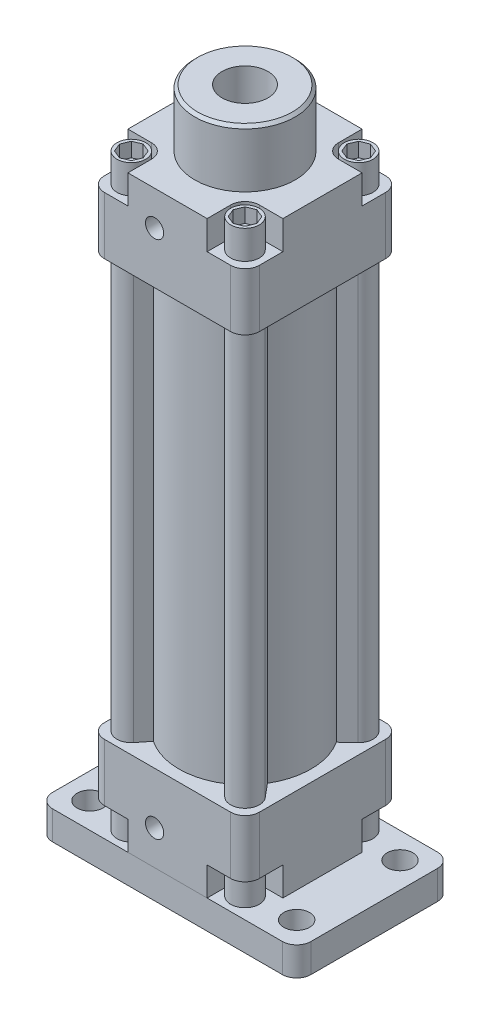
SolidWorks part; units mm, degrees
ref_plane "Front Plane" through (0, 0, 0) normal (0, 0, 1) x (1, 0, 0)
ref_plane "Top Plane" through (0, 0, 0) normal (0, 1, 0) x (1, 0, 0)
ref_plane "Right Plane" through (0, 0, 0) normal (1, 0, 0) x (0, 0, -1)
sketch "Sketch1" plane through (0, 0, 0) normal (0, 1, 0) x (1, 0, 0)
  line L1 (-27, 27) -> (27, 27)
  line L2 (-27, 27) -> (-27, -27)
  line L3 (-27, -27) -> (27, -27)
  line L4 (27, 27) -> (27, -27)
  line L5 (-27, 27) -> (27, -27) construction
  line L6 (-27, -27) -> (27, 27) construction
  point P0 (0, 0)
  dimension "D1" = 54
  dimension "D2" = 54
extrude "Boss-Extrude1" add sketch "Sketch1" along normal blind 20
sketch "Sketch2" plane through (0, 0, 0) normal (0, -1, 0) x (1, 0, 0)
  line L0 (0, 52.3019) -> (0, -54.3704) construction
  line L1 (-79.2133, 0) -> (82.1089, 0) construction
  line L2 (0, 0) -> (32.1456, -32.1456) construction
  line L3 (0, 0) -> (32.1456, 32.1456) construction
  line L4 (-13.799, 23.799) -> (-13.799, 27)
  line L5 (13.799, 23.799) -> (13.799, 27)
  line L6 (-13.799, 27) -> (13.799, 27)
  line L8 (-23.799, 13.799) -> (-27, 13.799)
  line L9 (-23.3345, 23.3345) -> (24.799, -24.799) construction
  line L10 (-24.799, -24.799) -> (24.799, 24.799) construction
  line L11 (-23.799, -13.799) -> (-27, -13.799)
  line L12 (-27, 13.799) -> (-27, -13.799)
  line L13 (-27, -27) -> (-27, 27) construction
  line L14 (-13.799, -23.799) -> (-13.799, -27)
  line L15 (-11.7092, 25.4341) -> (11.7092, -25.4341) construction
  line L16 (-11.7092, -25.4341) -> (11.7092, 25.4341) construction
  line L17 (27, -27) -> (-27, -27) construction
  line L18 (-13.799, -27) -> (13.799, -27)
  line L19 (13.799, -27) -> (13.799, -23.799)
  line L20 (23.799, 13.799) -> (27, 13.799)
  line L21 (-26.5996, 8.7444) -> (26.5996, -8.7444) construction
  line L22 (-26.5996, -8.7444) -> (26.5996, 8.7444) construction
  line L23 (13.799, 23.799) -> (13.799, 13.799)
  line L24 (13.799, 13.799) -> (23.799, 13.799)
  line L25 (27, 27) -> (27, -27) construction
  line L26 (13.799, -13.799) -> (23.799, -13.799)
  line L27 (13.799, -13.799) -> (13.799, -23.799)
  line L28 (27, 13.799) -> (27, -13.799)
  line L29 (-13.799, -13.799) -> (-13.799, -23.799)
  line L30 (-23.799, -13.799) -> (-13.799, -13.799)
  line L31 (27, -13.799) -> (23.799, -13.799)
  line L32 (-23.799, 13.799) -> (-13.799, 13.799)
  line L33 (-13.799, 23.799) -> (-13.799, 13.799)
  circle A1 centre (0, 0) radius 28 construction
  circle A2 centre (19.799, 19.799) radius 5
  circle A3 centre (19.799, -19.799) radius 5
  circle A4 centre (-19.799, -19.799) radius 5
  circle A5 centre (-19.799, 19.799) radius 5
  dimension "D2" = 56
  dimension "D3" = 10
  dimension "D4" = 10
extrude "Boss-Extrude2" add sketch "Sketch2" along normal blind 10
fillet "Fillet1" radius 5 4 edges at (13.799, -5, 13.799) (13.799, -5, -13.799) (-13.799, -5, -13.799) (-13.799, -5, 13.799)
fillet "Fillet3" radius 5 4 edges at (-27, 10, -27) (27, 10, -27) (27, 10, 27) (-27, 10, 27)
sketch "Sketch3" plane through (0, -10, 0) normal (0, -1, 0) x (1, 0, 0)
  line L0 (15.6496, 19.799) -> (16.8649, 16.8649)
  line L1 (19.799, 15.6496) -> (22.7331, 16.8649)
  line L2 (22.7331, 16.8649) -> (23.9484, 19.799)
  line L3 (23.9484, 19.799) -> (22.7331, 22.7331)
  line L4 (22.7331, 22.7331) -> (19.799, 23.9484)
  line L5 (19.799, 23.9484) -> (16.8649, 22.7331)
  line L6 (16.8649, 22.7331) -> (15.6496, 19.799)
  line L7 (16.8649, 16.8649) -> (19.799, 15.6496)
  line L8 (0, 37.5515) -> (0, -39.2541) construction
  line L9 (-65.2658, 0) -> (48.24, 0) construction
  line L10 (-16.8649, 16.8649) -> (-19.799, 15.6496)
  line L11 (-16.8649, 22.7331) -> (-15.6496, 19.799)
  line L12 (-19.799, 23.9484) -> (-16.8649, 22.7331)
  line L13 (-22.7331, 22.7331) -> (-19.799, 23.9484)
  line L14 (-23.9484, 19.799) -> (-22.7331, 22.7331)
  line L15 (-22.7331, 16.8649) -> (-23.9484, 19.799)
  line L16 (-19.799, 15.6496) -> (-22.7331, 16.8649)
  line L17 (-15.6496, 19.799) -> (-16.8649, 16.8649)
  line L18 (-15.6496, -19.799) -> (-16.8649, -16.8649)
  line L19 (-19.799, -15.6496) -> (-22.7331, -16.8649)
  line L20 (-22.7331, -16.8649) -> (-23.9484, -19.799)
  line L21 (-23.9484, -19.799) -> (-22.7331, -22.7331)
  line L22 (-22.7331, -22.7331) -> (-19.799, -23.9484)
  line L23 (-19.799, -23.9484) -> (-16.8649, -22.7331)
  line L24 (-16.8649, -22.7331) -> (-15.6496, -19.799)
  line L25 (-16.8649, -16.8649) -> (-19.799, -15.6496)
  line L26 (16.8649, -16.8649) -> (19.799, -15.6496)
  line L27 (16.8649, -22.7331) -> (15.6496, -19.799)
  line L28 (19.799, -23.9484) -> (16.8649, -22.7331)
  line L29 (22.7331, -22.7331) -> (19.799, -23.9484)
  line L30 (23.9484, -19.799) -> (22.7331, -22.7331)
  line L31 (22.7331, -16.8649) -> (23.9484, -19.799)
  line L32 (19.799, -15.6496) -> (22.7331, -16.8649)
  line L33 (15.6496, -19.799) -> (16.8649, -16.8649)
  circle A0 centre (19.799, 19.799) radius 3.8336 construction
  circle A1 centre (-19.799, 19.799) radius 3.8336 construction
  circle A2 centre (-19.799, -19.799) radius 3.8336 construction
  circle A3 centre (19.799, -19.799) radius 3.8336 construction
extrude "Cut-Extrude1" cut sketch "Sketch3" against normal blind 5
sketch "Sketch4" plane through (0, -10, 0) normal (0, -1, 0) x (1, 0, 0)
  circle A0 centre (0, 0) radius 17.5
  dimension "D1" = 35
extrude "Boss-Extrude3" add sketch "Sketch4" along normal blind 5.5
chamfer "Chamfer1" distance 1 angle 45 1 edges at (0, -15.5, -17.5)
sketch "Sketch5" plane through (0, 20, 0) normal (0, 1, 0) x (1, 0, 0)
  line L0 (16.8649, 16.8649) -> (15.6496, 19.799) construction
  line L1 (15.6496, 19.799) -> (16.8649, 22.7331) construction
  line L2 (16.8649, 22.7331) -> (19.799, 23.9484) construction
  line L3 (19.799, 23.9484) -> (22.7331, 22.7331) construction
  line L4 (22.7331, 22.7331) -> (23.9484, 19.799) construction
  line L5 (23.9484, 19.799) -> (22.7331, 16.8649) construction
  line L6 (22.7331, 16.8649) -> (19.799, 15.6496) construction
  line L7 (19.799, 15.6496) -> (16.8649, 16.8649) construction
  line L8 (-16.8649, 22.7331) -> (-15.6496, 19.799) construction
  line L9 (-15.6496, 19.799) -> (-16.8649, 16.8649) construction
  line L11 (-19.799, 15.6496) -> (-22.7331, 16.8649) construction
  line L12 (-22.7331, 16.8649) -> (-23.9484, 19.799) construction
  line L13 (-23.9484, 19.799) -> (-22.7331, 22.7331) construction
  line L14 (-22.7331, 22.7331) -> (-19.799, 23.9484) construction
  line L15 (-19.799, 23.9484) -> (-16.8649, 22.7331) construction
  line L16 (-16.8649, -16.8649) -> (-15.6496, -19.799) construction
  line L17 (-15.6496, -19.799) -> (-16.8649, -22.7331) construction
  line L18 (-16.8649, -22.7331) -> (-19.799, -23.9484) construction
  line L19 (-19.799, -23.9484) -> (-22.7331, -22.7331) construction
  line L20 (-22.7331, -22.7331) -> (-23.9484, -19.799) construction
  line L21 (-23.9484, -19.799) -> (-22.7331, -16.8649) construction
  line L22 (-22.7331, -16.8649) -> (-19.799, -15.6496) construction
  line L23 (-19.799, -15.6496) -> (-16.8649, -16.8649) construction
  line L24 (16.8649, -16.8649) -> (19.799, -15.6496) construction
  line L25 (19.799, -15.6496) -> (22.7331, -16.8649) construction
  line L26 (22.7331, -16.8649) -> (23.9484, -19.799) construction
  line L27 (23.9484, -19.799) -> (22.7331, -22.7331) construction
  line L28 (22.7331, -22.7331) -> (19.799, -23.9484) construction
  line L29 (19.799, -23.9484) -> (16.8649, -22.7331) construction
  line L30 (16.8649, -22.7331) -> (15.6496, -19.799) construction
  line L31 (15.6496, -19.799) -> (16.8649, -16.8649) construction
  line L32 (16.8649, 16.8649) -> (15.6496, 19.799) construction
  line L33 (15.6496, 19.799) -> (16.8649, 22.7331) construction
  line L34 (16.8649, 22.7331) -> (19.799, 23.9484) construction
  line L35 (19.799, 23.9484) -> (22.7331, 22.7331) construction
  line L36 (22.7331, 22.7331) -> (23.9484, 19.799) construction
  line L37 (23.9484, 19.799) -> (22.7331, 16.8649) construction
  line L38 (22.7331, 16.8649) -> (19.799, 15.6496) construction
  line L39 (19.799, 15.6496) -> (16.8649, 16.8649) construction
  line L40 (-16.8649, 22.7331) -> (-15.6496, 19.799) construction
  line L41 (-15.6496, 19.799) -> (-16.8649, 16.8649) construction
  line L43 (-19.799, 15.6496) -> (-22.7331, 16.8649) construction
  line L44 (-22.7331, 16.8649) -> (-23.9484, 19.799) construction
  line L45 (-23.9484, 19.799) -> (-22.7331, 22.7331) construction
  line L46 (-22.7331, 22.7331) -> (-19.799, 23.9484) construction
  line L47 (-19.799, 23.9484) -> (-16.8649, 22.7331) construction
  line L48 (-16.8649, -16.8649) -> (-15.6496, -19.799) construction
  line L49 (-15.6496, -19.799) -> (-16.8649, -22.7331) construction
  line L50 (-16.8649, -22.7331) -> (-19.799, -23.9484) construction
  line L51 (-19.799, -23.9484) -> (-22.7331, -22.7331) construction
  line L52 (-22.7331, -22.7331) -> (-23.9484, -19.799) construction
  line L53 (-23.9484, -19.799) -> (-22.7331, -16.8649) construction
  line L54 (-22.7331, -16.8649) -> (-19.799, -15.6496) construction
  line L55 (-19.799, -15.6496) -> (-16.8649, -16.8649) construction
  line L56 (16.8649, -16.8649) -> (19.799, -15.6496) construction
  line L57 (19.799, -15.6496) -> (22.7331, -16.8649) construction
  line L58 (22.7331, -16.8649) -> (23.9484, -19.799) construction
  line L59 (23.9484, -19.799) -> (22.7331, -22.7331) construction
  line L60 (22.7331, -22.7331) -> (19.799, -23.9484) construction
  line L61 (19.799, -23.9484) -> (16.8649, -22.7331) construction
  line L62 (16.8649, -22.7331) -> (15.6496, -19.799) construction
  line L63 (15.6496, -19.799) -> (16.8649, -16.8649) construction
  line L64 (0, 37.228) -> (0, -36.6187) construction
  line L65 (-48.6037, 0) -> (44.6355, 0) construction
  line L66 (-15.7483, 22.7302) -> (-13.0201, 18.9599)
  line L67 (-23.6809, 16.6476) -> (-19.7437, 11.7978)
  line L68 (15.9777, 23.0236) -> (12.7197, 19.1627)
  line L69 (19.6961, -11.877) -> (23.6362, -16.5934)
  line L70 (23.1924, 16.1268) -> (19.2921, 12.5226)
  line L71 (12.7406, -19.1488) -> (15.9618, -23.0046)
  line L72 (-15.8821, -22.9068) -> (-12.845, -19.0789)
  line L73 (-19.41, -12.339) -> (-23.3345, -16.2635)
  circle A0 centre (0, 0) radius 20
  arc A1 (-19.7437, 11.7978) -> (-19.41, -12.339) centre (0, 0) ccw
  arc A2 (-15.7483, 22.7302) -> (-23.6809, 16.6476) centre (-19.799, 19.799) ccw
  arc A3 (15.9777, 23.0236) -> (23.1924, 16.1268) centre (19.799, 19.799) cw
  arc A4 (15.9618, -23.0046) -> (23.6362, -16.5934) centre (19.799, -19.799) ccw
  arc A5 (-15.8821, -22.9068) -> (-23.3345, -16.2635) centre (-19.799, -19.799) cw
  arc A6 (12.7197, 19.1627) -> (-13.0201, 18.9599) centre (0, 0) ccw
  arc A7 (19.6961, -11.877) -> (19.2921, 12.5226) centre (0, 0) ccw
  arc A8 (-12.845, -19.0789) -> (12.7406, -19.1488) centre (0, 0) ccw
  circle A9 centre (-19.799, 19.799) radius 2.5
  circle A10 centre (19.799, 19.799) radius 2.5
  circle A11 centre (19.799, -19.799) radius 2.5
  circle A12 centre (-19.799, -19.799) radius 2.5
  dimension "D1" = 40
  dimension "D2" = 46
  dimension "D3" = 5
extrude "Boss-Extrude4" add sketch "Sketch5" along normal blind 145
sketch "Sketch20" plane through (0, 20, 0) normal (0, 1, 0) x (1, 0, 0)
  circle A1 centre (0, 0) radius 20
  circle A2 centre (0, 0) radius 20
  dimension "D1" = 0
extrude "Cut-Extrude3" cut sketch "Sketch20" against normal blind 22 and the other way blind 168
sketch "Sketch9" plane through (0, 165, 0) normal (0, 1, 0) x (1, 0, 0)
  line L4 (22, 27) -> (-22, 27)
  line L5 (-27, 22) -> (-27, -22)
  line L6 (-22, -27) -> (22, -27)
  line L7 (27, -22) -> (27, 22)
  line L8 (22, 27) -> (-22, 27)
  line L9 (-27, 22) -> (-27, -22)
  line L10 (-22, -27) -> (22, -27)
  line L11 (27, -22) -> (27, 22)
  arc A4 (-22, 27) -> (-27, 22) centre (-22, 22) ccw
  arc A5 (-27, -22) -> (-22, -27) centre (-22, -22) ccw
  arc A6 (22, -27) -> (27, -22) centre (22, -22) ccw
  arc A7 (27, 22) -> (22, 27) centre (22, 22) ccw
  arc A8 (-22, 27) -> (-27, 22) centre (-22, 22) ccw
  arc A9 (-27, -22) -> (-22, -27) centre (-22, -22) ccw
  arc A10 (22, -27) -> (27, -22) centre (22, -22) ccw
  arc A11 (27, 22) -> (22, 27) centre (22, 22) ccw
  dimension "D1" = 0
extrude "Boss-Extrude5" add sketch "Sketch9" along normal blind 20
hole_wizard "Ø5.0 (5) Diameter Hole2" positions "Sketch14" profile "Sketch13" hole size "Ø5.0" standard "ANSI Metric"
sketch "Sketch14" plane through (0, -5, 0) normal (0, -1, 0) x (-1, 0, 0)
  point P0 (-19.799, 19.799)
  point P3 (-19.799, -19.799)
  point P6 (19.799, 19.799)
  point P9 (19.799, -19.799)
sketch "Sketch13" plane through (19.799, -5, -19.799) normal (1, 0, 0) x (0, 0, -1)
  line L0 (0, 0) -> (0, 14.5022)
  line L1 (0, 14.5022) -> (2.5, 13)
  line L2 (2.5, 13) -> (2.5, 0)
  line L5 (2.5, 0) -> (0, 0)
  line L10 (0, 14.5022) -> (-2.5, 13) construction
  line L11 (0, -6.35) -> (0, 107.95) construction
  dimension "Hole Dia." = 5
  dimension "Hole Depth" = 13
  dimension "Drill Angle" = 118
sketch "Sketch15" plane through (0, 185, 0) normal (0, 1, 0) x (1, 0, 0)
  line L12 (-27, -13.799) -> (-18.799, -13.799)
  line L13 (-13.799, -27) -> (13.799, -27)
  line L14 (-18.799, 13.799) -> (-27, 13.799)
  line L15 (-13.799, 27) -> (-13.799, 18.799)
  line L16 (-13.799, -27) -> (13.799, -27)
  line L17 (13.799, 18.799) -> (13.799, 27)
  line L18 (27, 13.799) -> (18.799, 13.799)
  line L19 (-27, 13.799) -> (-27, -13.799)
  line L20 (18.799, -13.799) -> (27, -13.799)
  line L21 (13.799, -27) -> (13.799, -18.799)
  line L22 (-27, 13.799) -> (-27, -13.799)
  line L23 (-13.799, -18.799) -> (-13.799, -27)
  line L24 (-27, -13.799) -> (-18.799, -13.799)
  line L25 (13.799, 27) -> (-13.799, 27)
  line L26 (-18.799, 13.799) -> (-27, 13.799)
  line L27 (-13.799, 27) -> (-13.799, 18.799)
  line L28 (13.799, 27) -> (-13.799, 27)
  line L29 (13.799, 18.799) -> (13.799, 27)
  line L30 (27, 13.799) -> (18.799, 13.799)
  line L31 (27, -13.799) -> (27, 13.799)
  line L32 (18.799, -13.799) -> (27, -13.799)
  line L33 (13.799, -27) -> (13.799, -18.799)
  line L34 (27, -13.799) -> (27, 13.799)
  line L35 (-13.799, -18.799) -> (-13.799, -27)
  circle A0 centre (-19.799, 19.799) radius 5 construction
  circle A1 centre (19.799, 19.799) radius 5 construction
  circle A2 centre (19.799, -19.799) radius 5 construction
  circle A3 centre (-19.799, -19.799) radius 5 construction
  circle A4 centre (-19.799, 19.799) radius 5
  circle A5 centre (19.799, 19.799) radius 5
  circle A6 centre (19.799, -19.799) radius 5
  circle A7 centre (-19.799, -19.799) radius 5
  arc A22 (-18.799, 13.799) -> (-13.799, 18.799) centre (-18.799, 18.799) ccw
  arc A25 (13.799, 18.799) -> (18.799, 13.799) centre (18.799, 18.799) ccw
  arc A28 (18.799, -13.799) -> (13.799, -18.799) centre (18.799, -18.799) ccw
  arc A31 (-13.799, -18.799) -> (-18.799, -13.799) centre (-18.799, -18.799) ccw
  arc A34 (-18.799, 13.799) -> (-13.799, 18.799) centre (-18.799, 18.799) ccw
  arc A37 (13.799, 18.799) -> (18.799, 13.799) centre (18.799, 18.799) ccw
  arc A40 (18.799, -13.799) -> (13.799, -18.799) centre (18.799, -18.799) ccw
  arc A43 (-13.799, -18.799) -> (-18.799, -13.799) centre (-18.799, -18.799) ccw
  dimension "D1" = 0
extrude "Boss-Extrude6" add sketch "Sketch15" along normal blind 10
sketch "Sketch16" plane through (0, 195, 0) normal (0, 1, 0) x (1, 0, 0)
  line L12 (16.8649, 22.7331) -> (19.799, 23.9484) construction
  line L13 (15.6496, 19.799) -> (16.8649, 22.7331) construction
  line L14 (16.8649, 16.8649) -> (15.6496, 19.799) construction
  line L15 (19.799, 15.6496) -> (16.8649, 16.8649) construction
  line L16 (23.9484, 19.799) -> (22.7331, 16.8649) construction
  line L17 (22.7331, 22.7331) -> (23.9484, 19.799) construction
  line L18 (19.799, 23.9484) -> (22.7331, 22.7331) construction
  line L19 (22.7331, 16.8649) -> (19.799, 15.6496) construction
  line L20 (16.8649, 22.7331) -> (19.799, 23.9484)
  line L21 (15.6496, 19.799) -> (16.8649, 22.7331)
  line L22 (16.8649, 16.8649) -> (15.6496, 19.799)
  line L23 (19.799, 15.6496) -> (16.8649, 16.8649)
  line L24 (23.9484, 19.799) -> (22.7331, 16.8649)
  line L25 (22.7331, 22.7331) -> (23.9484, 19.799)
  line L26 (19.799, 23.9484) -> (22.7331, 22.7331)
  line L27 (22.7331, 16.8649) -> (19.799, 15.6496)
  line L28 (0, 36.7948) -> (0, -40.3891) construction
  line L29 (-55.2395, 0) -> (47.4833, 0) construction
  line L30 (-22.7331, 16.8649) -> (-19.799, 15.6496)
  line L31 (-19.799, 23.9484) -> (-22.7331, 22.7331)
  line L32 (-22.7331, 22.7331) -> (-23.9484, 19.799)
  line L33 (-23.9484, 19.799) -> (-22.7331, 16.8649)
  line L34 (-19.799, 15.6496) -> (-16.8649, 16.8649)
  line L35 (-16.8649, 16.8649) -> (-15.6496, 19.799)
  line L36 (-15.6496, 19.799) -> (-16.8649, 22.7331)
  line L37 (-16.8649, 22.7331) -> (-19.799, 23.9484)
  line L38 (-16.8649, -22.7331) -> (-19.799, -23.9484)
  line L39 (-15.6496, -19.799) -> (-16.8649, -22.7331)
  line L40 (-16.8649, -16.8649) -> (-15.6496, -19.799)
  line L41 (-19.799, -15.6496) -> (-16.8649, -16.8649)
  line L42 (-23.9484, -19.799) -> (-22.7331, -16.8649)
  line L43 (-22.7331, -22.7331) -> (-23.9484, -19.799)
  line L44 (-19.799, -23.9484) -> (-22.7331, -22.7331)
  line L45 (-22.7331, -16.8649) -> (-19.799, -15.6496)
  line L46 (22.7331, -16.8649) -> (19.799, -15.6496)
  line L47 (19.799, -23.9484) -> (22.7331, -22.7331)
  line L48 (22.7331, -22.7331) -> (23.9484, -19.799)
  line L49 (23.9484, -19.799) -> (22.7331, -16.8649)
  line L50 (19.799, -15.6496) -> (16.8649, -16.8649)
  line L51 (16.8649, -16.8649) -> (15.6496, -19.799)
  line L52 (15.6496, -19.799) -> (16.8649, -22.7331)
  line L53 (16.8649, -22.7331) -> (19.799, -23.9484)
extrude "Cut-Extrude2" cut sketch "Sketch16" against normal blind 5
hole_wizard "Ø5.0 (5) Diameter Hole3" positions "Sketch18" profile "Sketch17" hole size "Ø5.0" standard "ANSI Metric"
sketch "Sketch18" plane through (0, 190, 0) normal (0, 1, 0) x (1, 0, 0)
  point P0 (-19.9728, 19.799)
  point P2 (-19.799, -19.799)
  point P5 (19.799, -19.799)
  point P8 (19.799, 19.799)
sketch "Sketch17" plane through (-19.9728, 190, -19.799) normal (1, 0, 0) x (0, 0, 1)
  line L0 (0, 0) -> (0, 14.5022)
  line L1 (0, 14.5022) -> (2.5, 13)
  line L2 (2.5, 13) -> (2.5, 0)
  line L5 (2.5, 0) -> (0, 0)
  line L10 (0, 14.5022) -> (-2.5, 13) construction
  line L11 (0, -6.35) -> (0, 107.95) construction
  dimension "Hole Dia." = 5
  dimension "Hole Depth" = 13
  dimension "Drill Angle" = 118
sketch "Sketch21" plane through (0, 165, 0) normal (0, -1, 0) x (1, 0, 0)
  circle A0 centre (0, 0) radius 20
  dimension "D1" = 40
extrude "Cut-Extrude4" cut sketch "Sketch21" against normal blind 24
sketch "Sketch22" plane through (0, 0, 27) normal (0, 0, 1) x (1, 0, 0)
  line L0 (0, 235.3939) -> (0, -60.3185) construction
  line L1 (-13.799, 195) -> (13.799, 195) construction
  line L2 (-13.799, 195) -> (13.799, 195) construction
  line L3 (13.799, -10) -> (-13.799, -10) construction
  circle A0 centre (-4.5, 183) radius 3.175
  circle A1 centre (-4.5, 2) radius 3.175
  dimension "D3" = 6.35
  dimension "D4" = 6.35
  dimension "D1" = 12
  dimension "D2" = 4.5
  dimension "D5" = 4.5
  dimension "D6" = 12
extrude "Cut-Extrude5" cut sketch "Sketch22" against normal blind 24
sketch "Sketch23" plane through (0, 195, 0) normal (0, 1, 0) x (1, 0, 0)
  circle A0 centre (0, 0) radius 17.5
  dimension "D1" = 35
extrude "Boss-Extrude7" add sketch "Sketch23" along normal blind 20
chamfer "Chamfer2" distance 1 angle 45 1 edges at (0, 215, 17.5)
sketch "Sketch26" plane through (0, 215, 0) normal (0, 1, 0) x (1, 0, 0)
  circle A0 centre (0, 0) radius 8
  dimension "D1" = 16
extrude "Cut-Extrude6" cut sketch "Sketch26" against normal blind 169
sketch "Sketch27" plane through (0, -10, 0) normal (0, -1, 0) x (1, 0, 0)
  line L0 (0, 35.8833) -> (0, -39.6688) construction
  line L1 (-45, 27) -> (45, 27)
  line L2 (-45, 27) -> (-45, -27)
  line L3 (-45, -27) -> (45, -27)
  line L4 (45, 27) -> (45, -27)
  line L5 (-45, 27) -> (45, -27) construction
  line L6 (-45, -27) -> (45, 27) construction
  line L7 (-53.675, 0) -> (68.7898, 0) construction
  circle A0 centre (0, 0) radius 17.5
  circle A1 centre (-19.799, 19.799) radius 5
  circle A2 centre (19.799, 19.799) radius 5
  circle A3 centre (19.799, -19.799) radius 5
  circle A4 centre (-19.799, -19.799) radius 5
  circle A5 centre (36, 18) radius 4.5
  circle A6 centre (36, -18) radius 4.5
  circle A7 centre (-36, -18) radius 4.5
  circle A8 centre (-36, 18) radius 4.5
  point P0 (0, 0)
  dimension "D3" = 9
  dimension "D1" = 90
  dimension "D2" = 54
  dimension "D4" = 36
  dimension "D5" = 36
extrude "Boss-Extrude9" add sketch "Sketch27" along normal blind 10 separate body
fillet "Fillet4" radius 5 4 edges at (-45, -15, 27) (45, -15, 27) (45, -15, -27) (-45, -15, -27)
